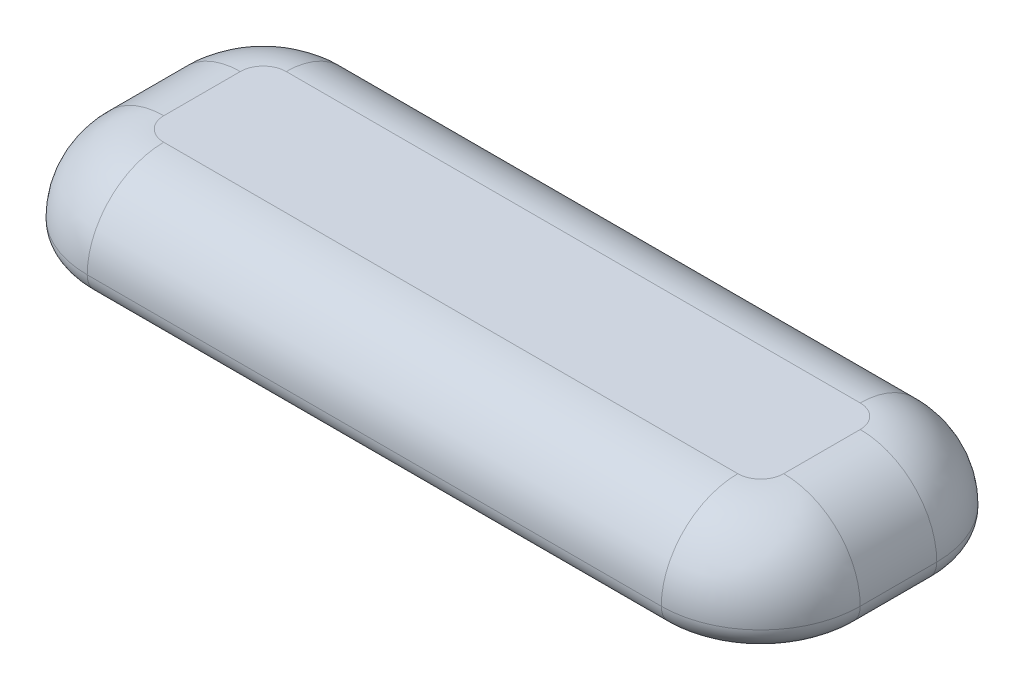
SolidWorks part; units mm, degrees
ref_plane "前视基准面" through (0, 0, 0) normal (0, 0, 1) x (1, 0, 0)
ref_plane "上视基准面" through (0, 0, 0) normal (0, 1, 0) x (1, 0, 0)
ref_plane "右视基准面" through (0, 0, 0) normal (1, 0, 0) x (0, 0, -1)
sketch "草图1" plane through (0, 0, 0) normal (0, 1, 0) x (1, 0, 0)
  line L1 (-37.5, 15) -> (37.5, 15)
  line L2 (-47.5, 5) -> (-47.5, -5)
  line L3 (-37.5, -15) -> (37.5, -15)
  line L4 (47.5, 5) -> (47.5, -5)
  line L5 (0, -15) -> (0, 15) construction
  line L6 (-47.5, 0) -> (47.5, 0) construction
  arc A0 (-47.5, -5) -> (-37.5, -15) centre (-37.5, -5) ccw
  arc A1 (-47.5, 5) -> (-37.5, 15) centre (-37.5, 5) cw
  arc A2 (37.5, 15) -> (47.5, 5) centre (37.5, 5) cw
  arc A3 (47.5, -5) -> (37.5, -15) centre (37.5, -5) cw
  point P0 (0, 0)
  point P8 (-47.5, 15)
  point P11 (47.5, 15)
  point P15 (47.5, -15)
  dimension "D3" = 10
  dimension "D1" = 95
  dimension "D2" = 30
extrude "凸台-拉伸1" add sketch "草图1" along normal blind 10
shell "抽壳2" thickness 3 removed face at (0, 0, 0) outward yes
fillet "圆角3" radius 10 8 edges at (46.6924, 13, -14.1924) (50.5, 13, 0) (46.6924, 13, 14.1924) (0, 13, 18) (-46.6924, 13, 14.1924) (-50.5, 13, 0) (-46.6924, 13, -14.1924) (0, 13, -18)
fillet "圆角4" radius 3 8 edges at (50.5, 0, 0) (46.6924, 0, 14.1924) (0, 0, 18) (-46.6924, 0, 14.1924) (-50.5, 0, 0) (-46.6924, 0, -14.1924) (0, 0, -18) (46.6924, 0, -14.1924)
ref_plane "基准面1" through (0, 10, 0) normal (0, -1, 0) x (-1, 0, 0)
sketch "草图2" plane through (0, 10, 0) normal (0, -1, 0) x (-1, 0, 0)
  line L0 (0, 0) -> (37, 0) construction
  line L1 (0, 0) -> (0, 6.5357) construction
  line L2 (34.95, 0.55) -> (39.05, 0.55)
  line L3 (34.95, 0.55) -> (34.95, -0.55)
  line L4 (34.95, -0.55) -> (39.05, -0.55)
  line L5 (39.05, 0.55) -> (39.05, -0.55)
  line L6 (37, -0.55) -> (37, 0.55) construction
  line L7 (34.95, 0) -> (39.05, 0) construction
  line L8 (36.45, 2.05) -> (37.55, 2.05)
  line L9 (36.45, 2.05) -> (36.45, -2.05)
  line L10 (36.45, -2.05) -> (37.55, -2.05)
  line L11 (37.55, 2.05) -> (37.55, -2.05)
  line L12 (37, -2.05) -> (37, 2.05) construction
  line L13 (36.45, 0) -> (37.55, 0) construction
  line L14 (-36.45, 0) -> (-37.55, 0) construction
  line L15 (-37, -2.05) -> (-37, 2.05) construction
  line L16 (-34.95, 0) -> (-39.05, 0) construction
  line L17 (-37, -0.55) -> (-37, 0.55) construction
  line L18 (-37.55, 2.05) -> (-37.55, -2.05)
  line L19 (-36.45, -2.05) -> (-37.55, -2.05)
  line L20 (-36.45, 2.05) -> (-36.45, -2.05)
  line L21 (-36.45, 2.05) -> (-37.55, 2.05)
  line L22 (-39.05, 0.55) -> (-39.05, -0.55)
  line L23 (-34.95, -0.55) -> (-39.05, -0.55)
  line L24 (-34.95, 0.55) -> (-34.95, -0.55)
  line L25 (-34.95, 0.55) -> (-39.05, 0.55)
  circle A0 centre (37, 0) radius 2.65
  circle A1 centre (-37, 0) radius 2.65
  dimension "D2" = 5.3
  dimension "D1" = 37
  dimension "D3" = 4.1
  dimension "D4" = 1.1
  dimension "D5" = 4.1
  dimension "D6" = 1.1
extrude "凸台-拉伸2" add sketch "草图2" along normal blind 8 contours A0 L8 L11 L2 L5 L4 L10 L9 L3 | A1 L25 L24 L23 L20 L19 L18 L22 L21 region at (-34.425, 10, 0) region at (39.575, 10, 0)
fillet "圆角7" radius 5 8 edges at (0, 10, 15) (44.5711, 10, 12.0711) (47.5, 10, 0) (44.5711, 10, -12.0711) (0, 10, -15) (-44.5711, 10, -12.0711) (-47.5, 10, 0) (-44.5711, 10, 12.0711)
chamfer "倒角1" distance 0.2 angle 45 12 edges at (37, 2, -2.05) (36.45, 2, -1.3) (35.7, 2, -0.55) (34.95, 2, 0) (35.7, 2, 0.55) (36.45, 2, 1.3) (37, 2, 2.05) (37.55, 2, 1.3) (38.3, 2, 0.55) (39.05, 2, 0) (38.3, 2, -0.55) (37.55, 2, -1.3)
chamfer "倒角2" distance 0.2 angle 45 12 edges at (-36.45, 2, -1.3) (-35.7, 2, -0.55) (-34.95, 2, 0) (-35.7, 2, 0.55) (-36.45, 2, 1.3) (-37, 2, 2.05) (-37.55, 2, 1.3) (-38.3, 2, 0.55) (-39.05, 2, 0) (-38.3, 2, -0.55) (-37.55, 2, -1.3) (-37, 2, -2.05)
fillet "圆角9" radius 2 1 edges at (37, 10, -2.65)
fillet "圆角10" radius 2 1 edges at (-37, 10, 2.65)
